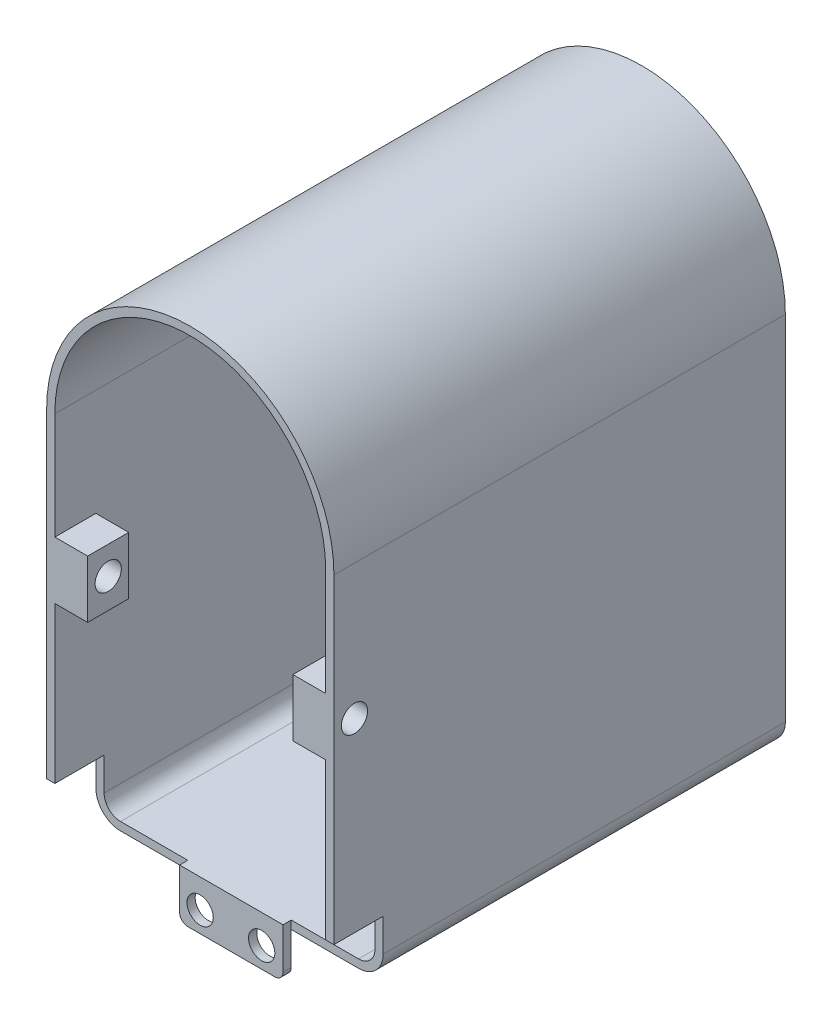
SolidWorks part; units mm, degrees
ref_plane "정면" through (0, 0, 0) normal (0, 0, 1) x (1, 0, 0)
ref_plane "윗면" through (0, 0, 0) normal (0, 1, 0) x (1, 0, 0)
ref_plane "우측면" through (0, 0, 0) normal (1, 0, 0) x (0, 0, -1)
sketch "스케치1" plane through (0, 0, 0) normal (0, 0, 1) x (1, 0, 0)
  line L1 (0, 0) -> (35, 0)
  line L2 (0, 0) -> (0, 46)
  line L4 (35, 0) -> (35, 46)
  arc A0 (35, 46) -> (0, 46) centre (17.5, 46) ccw
  dimension "D1" = 35
  dimension "D2" = 46
extrude "보스-돌출1" add sketch "스케치1" along normal blind 55
fillet "필렛4" radius 3 2 edges at (0, 0, 27.5) (35, 0, 27.5)
shell "쉘1" thickness 1 removed face at (17.5, 19.0429, 55)
sketch "스케치3" plane through (0, 0, 0) normal (0, -1, 0) x (1, 0, 0)
  line L1 (0, 49) -> (35, 49)
  line L2 (0, 49) -> (0, 55)
  line L3 (0, 55) -> (35, 55)
  line L4 (35, 49) -> (35, 55)
  line L9 (3, 55) -> (32, 55) construction
  line L10 (0, 55) -> (0, 0) construction
  line L11 (35, 55) -> (35, 0) construction
  dimension "D1" = 6
extrude "컷-돌출2" cut sketch "스케치3" against normal blind 7
sketch "스케치4" plane through (0, 0, 49) normal (0, 0, 1) x (1, 0, 0)
  line L0 (3, 1) -> (32, 1) construction
  line L1 (11.2, 1) -> (23.8, 1)
  line L2 (11.2, 1) -> (11.2, -5)
  line L3 (11.2, -5) -> (23.8, -5)
  line L4 (23.8, 1) -> (23.8, -5)
  line L5 (35, 7) -> (35, 46) construction
  line L6 (13.7, -2.5) -> (21.2, -2.5) construction
  circle A0 centre (13.7, -2.5) radius 1.6
  circle A1 centre (21.2, -2.5) radius 1.6
  dimension "D4" = 2.5
  dimension "D6" = 3.2
  dimension "D7" = 2.5
  dimension "D1" = 6
  dimension "D2" = 12.6
  dimension "D3" = 11.2
  dimension "D5" = 7.5
extrude "보스-돌출2" add sketch "스케치4" along normal blind 1
fillet "필렛5" radius 1 2 edges at (23.8, -5, 49.5) (11.2, -5, 49.5)
sketch "스케치5" plane through (0, 0, 55) normal (0, 0, 1) x (1, 0, 0)
  line L0 (0, 46) -> (0, 7) construction
  line L1 (0, 33) -> (5, 33)
  line L2 (0, 33) -> (0, 26)
  line L3 (0, 26) -> (5, 26)
  line L4 (5, 33) -> (5, 26)
  line L5 (35, 7) -> (35, 46) construction
  line L6 (35, 33) -> (30, 33)
  line L7 (35, 33) -> (35, 26)
  line L8 (35, 26) -> (30, 26)
  line L9 (30, 33) -> (30, 26)
  line L10 (3, 0) -> (11.2, 0) construction
  dimension "D1" = 5
  dimension "D2" = 5
  dimension "D3" = 33
  dimension "D4" = 7
extrude "보스-돌출3" add sketch "스케치5" against normal blind 5
sketch "스케치7" plane through (0, 0, 0) normal (-1, 0, 0) x (0, 0, 1)
  line L0 (55, 26) -> (55, 33) construction
  line L1 (50, 33) -> (55, 33) construction
  circle A0 centre (52.5, 29.615) radius 1.6
  dimension "D1" = 3.2
  dimension "D2" = 2.5
  dimension "D3" = 3.385
extrude "컷-돌출3" cut sketch "스케치7" against normal through all
